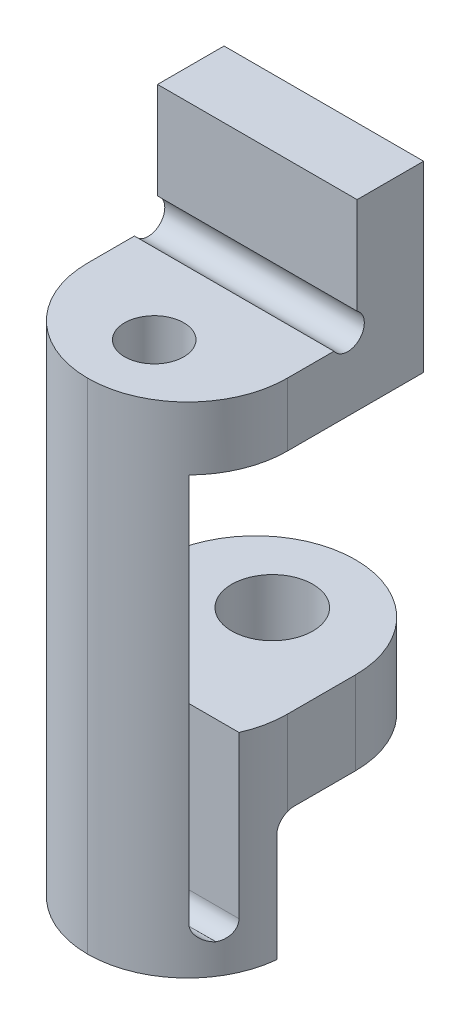
SolidWorks part; units mm, degrees
material "Copper"
ref_plane "Front Plane" through (0, 0, 0) normal (0, 0, 1) x (1, 0, 0)
ref_plane "Top Plane" through (0, 0, 0) normal (0, 1, 0) x (1, 0, 0)
ref_plane "Right Plane" through (0, 0, 0) normal (1, 0, 0) x (0, 0, -1)
ref_plane "Plane1" through (7.5, 0, 0) normal (1, 0, 0) x (0, 0, -1)
sketch "Sketch1" plane through (7.5, 0, 0) normal (1, 0, 0) x (0, 0, -1)
  line L1 (-13.9787, 18.1646) -> (-13.9787, -4.4024)
  line L7 (-13.9787, -4.4024) -> (7, -4.4024)
  line L12 (7, 18.1646) -> (-13.9787, 18.1646)
  line L14 (7, 18.1646) -> (7, -4.4024)
  line L15 (-13.9787, 5.8146) -> (-6.902, 5.8146)
  line L16 (-13.9787, 18.1646) -> (-6.902, 18.1646)
  line L17 (-13.9787, 18.1646) -> (-13.9787, 12.6646)
  line L18 (-13.9787, 12.6646) -> (-6.902, 12.6646)
  line L19 (-6.902, 18.1646) -> (-6.902, 12.6646)
  line L24 (7, 18.1646) -> (0.198, 18.1646)
  line L25 (7, 18.1646) -> (7, 12.6646)
  line L26 (7, 12.6646) -> (0.198, 12.6646)
  line L27 (0.198, 18.1646) -> (0.198, 12.6646)
  line L28 (-6.902, 18.1646) -> (-1.802, 18.1646)
  line L29 (-6.902, 18.1646) -> (-6.902, 14.5646)
  line L30 (-6.902, 14.5646) -> (-1.802, 14.5646)
  line L31 (-1.802, 18.1646) -> (-1.802, 14.5646)
  line L32 (7, 12.6646) -> (-6.002, 12.6646)
  line L33 (7, 12.6646) -> (7, 5.8146)
  line L34 (7, 5.8146) -> (-6.002, 5.8146)
  line L35 (-6.002, 12.6646) -> (-6.002, 5.8146)
  line L36 (-13.9787, 12.6646) -> (-6.902, 12.6646)
  line L37 (-13.9787, 12.6646) -> (-13.9787, 5.8146)
  line L40 (-6.902, 5.8146) -> (-6.902, 12.6646)
  line L41 (-6.902, 12.6646) -> (-13.9787, 12.6646)
  line L43 (-13.9787, -4.4024) -> (7, -4.4024)
  line L44 (-13.9787, -4.4024) -> (-13.9787, -0.4354)
  line L45 (-13.9787, -0.4354) -> (7, -0.4354)
  line L46 (7, -4.4024) -> (7, -0.4354)
  line L47 (-6.902, 5.8146) -> (-13.9787, 5.8146)
  line L48 (-6.902, 5.8146) -> (-6.902, -0.4354)
  line L49 (-6.902, -0.4354) -> (-13.9787, -0.4354)
  line L50 (-13.9787, 5.8146) -> (-13.9787, -0.4354)
  line L51 (-6.002, 5.8146) -> (-5.102, 5.8146)
  line L52 (-6.002, 5.8146) -> (-6.002, 0.4646)
  line L53 (-6.002, 0.4646) -> (-5.102, 0.4646)
  line L54 (-5.102, 5.8146) -> (-5.102, 0.4646)
  line L55 (-4.202, -0.4354) -> (7, -0.4354)
  line L56 (-4.202, -0.4354) -> (-4.202, 3.3146)
  line L57 (-4.202, 3.3146) -> (7, 3.3146)
  line L58 (7, -0.4354) -> (7, 3.3146)
  line L59 (7, 5.8146) -> (1.148, 5.8146)
  line L60 (7, 5.8146) -> (7, 3.3146)
  line L61 (7, 3.3146) -> (1.148, 3.3146)
  line L62 (1.148, 5.8146) -> (1.148, 3.3146)
  dimension "D1" = 7.1
  dimension "D2" = 5.5
  dimension "D3" = 5.5
  dimension "D4" = 2
  dimension "D5" = 1.9
  dimension "D6" = 4.2
  dimension "D7" = 8.75
  dimension "D8" = 0.9
  dimension "D9" = 6.85
  dimension "D10" = 15
  dimension "D11" = 0.9
  dimension "D12" = 0.9
  dimension "D13" = 2.5
  dimension "D14" = 6.25
  dimension "D15" = 7.0767
  dimension "D16" = 0.9
extrude "Boss-Extrude1" add sketch "Sketch1" against normal blind 6 contours L12 L31 L30 L19 L18 L1 L7 L14 L26 L27 region at (7.5, 13.6146, 6.6994)
fillet "Fillet2" radius 3 4 edges at (1.5, 4.5646, -1.148) (7.5, 4.5646, -1.148) (1.5, 7.0646, 6.902) (7.5, 7.0646, 6.902) tangent propagation no
sketch "Sketch2" plane through (0, 14.5646, 0) normal (0, 1, 0) x (1, 0, 0)
  line L0 (1.5, -3.902) -> (1.5, -1.802) construction
  point P0 (4.5, -4.902)
  dimension "D1" = 2
  dimension "D2" = 3
hole_wizard "#2-56 Tapped Hole1" positions "Sketch2" profile "Sketch3" tap size "#2-56" standard "ANSI Inch" end condition up to next
sketch "Sketch3" plane through (4.5, 14.5646, 4.902) normal (1, 0, 0) x (0, 0, 1)
  line L0 (0, 0) -> (0, 1.9)
  line L1 (0, 1.9) -> (0.889, 1.9)
  line L2 (0.889, 1.9) -> (0.889, 0)
  line L5 (0.889, 0) -> (0, 0)
  line L11 (0, -6.35) -> (0, 107.95) construction
  dimension "Thru Tap Drill Dia." = 1.778
  dimension "Thru Tap Drill Depth" = 1.9
cosmetic thread "Hole Thread1" parameters "D2"=2.1844
sketch "Sketch4" plane through (0, 3.3146, 0) normal (0, -1, 0) x (-1, 0, 0)
  line L0 (-1.5, -3.902) -> (-1.5, -1.852) construction
  point P0 (-4.5, -1.352)
  dimension "D1" = 2.5
  dimension "D2" = 3
hole_wizard "#2 Clearance Hole1" positions "Sketch4" profile "Sketch5" hole size "#2" standard "ANSI Inch" end condition up to next
sketch "Sketch5" plane through (4.5, 3.3146, 1.352) normal (1, 0, 0) x (0, 0, -1)
  line L0 (0, 0) -> (0, 2.5)
  line L1 (0, 2.5) -> (1.2192, 2.5)
  line L2 (1.2192, 2.5) -> (1.2192, 0)
  line L5 (1.2192, 0) -> (0, 0)
  line L11 (0, -6.35) -> (0, 107.95) construction
  dimension "Thru Hole Dia." = 2.4384
  dimension "Thru Hole Depth" = 2.5
sketch "Sketch7" plane through (7.5, 0, 0) normal (1, 0, 0) x (0, 0, -1)
  line L0 (-1.802, 14.5646) -> (-2.0849, 14.8475)
  line L1 (-1.802, 18.1646) -> (-1.802, 14.5646) construction
  circle A0 centre (-2.0849, 14.8475) radius 0.5
  dimension "D1" = 0.4
  dimension "D3" = 1
  dimension "D2" = 45
extrude "Cut-Extrude1" cut sketch "Sketch7" against normal blind 10 contours A0
fillet "Fillet3" radius 0.5 3 edges at (4.5, 3.3146, 4.202) (4.5, 0.4646, 5.102) (4.5, 0.4646, 6.002)
